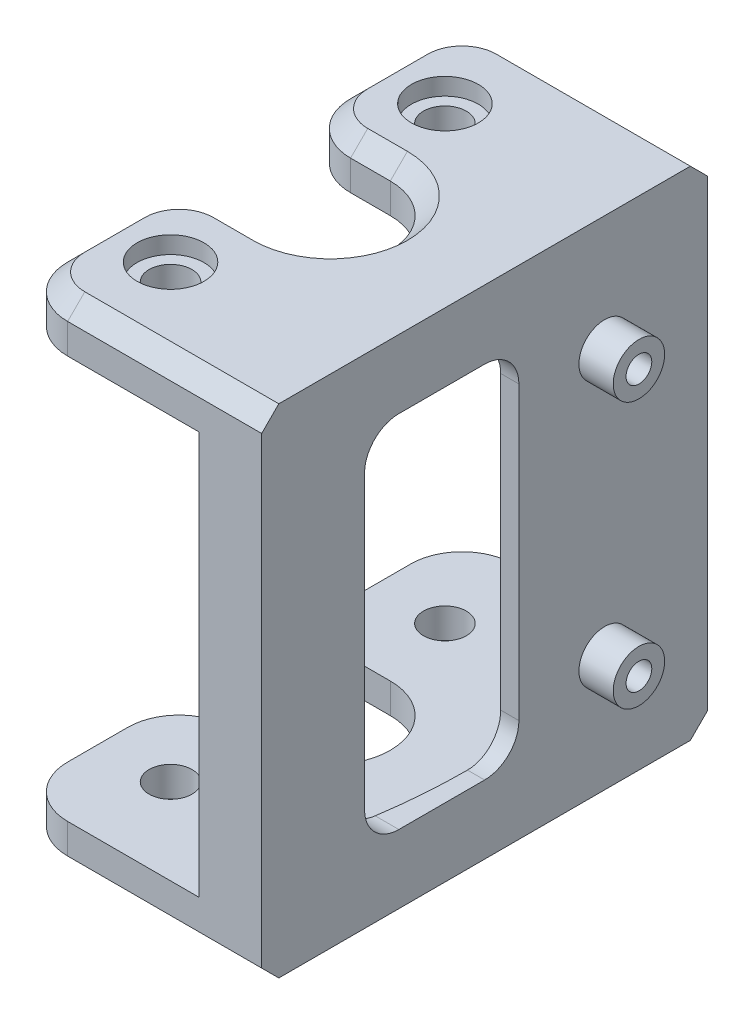
SolidWorks part; units mm, degrees
ref_plane "Спереди" through (0, 0, 0) normal (0, 0, 1) x (1, 0, 0)
ref_plane "Сверху" through (0, 0, 0) normal (0, 1, 0) x (1, 0, 0)
ref_plane "Справа" through (0, 0, 0) normal (1, 0, 0) x (0, 0, -1)
sketch "Эскиз1" plane through (0, 0, 0) normal (0, 1, 0) x (1, 0, 0)
  line L0 (23.6854, 8) -> (23.6854, -8) construction
  line L1 (19.6854, 13) -> (34, 13)
  line L2 (19.6854, 13) -> (19.6854, -13)
  line L3 (19.6854, -13) -> (34, -13)
  line L4 (34, 13) -> (34, -13)
  line L5 (19.6854, 13) -> (34, -13) construction
  line L6 (19.6854, -13) -> (34, 13) construction
  line L7 (25, 3.5) -> (19.6854, 3.5)
  line L8 (25, -3.5) -> (19.6854, -3.5)
  circle A0 centre (0, 0) radius 25 construction
  circle A1 centre (23.6854, 8) radius 1.25
  circle A2 centre (23.6854, -8) radius 1.25
  circle A3 centre (25, 0) radius 3.5
  point P3 (26.8427, 0)
  dimension "D1" = 50
  dimension "D2" = 2.5
  dimension "D3" = 2.5
  dimension "D8" = 7
  dimension "D4" = 16
  dimension "D5" = 4
  dimension "D6" = 34
  dimension "D7" = 26
extrude "Бобышка-Вытянуть1" add sketch "Эскиз1" along normal mid plane 29 contours A3 L8 L2 L3 L4 L1 L7 A2 A1 region at (26.8427, 0, -12.7032)
sketch "Эскиз2" plane through (0, 0, 0) normal (0, 1, 0) x (1, 0, 0)
  circle A0 centre (0, 0) radius 33
  dimension "D1" = 66
extrude "Вырез-Вытянуть1" cut sketch "Эскиз2" against normal mid plane 23.5 contours A0
sketch "Эскиз3" plane through (34, 0, 0) normal (1, 0, 0) x (0, 0, -1)
  line L0 (-13, 0) -> (13, 0) construction
  line L5 (-7, 10.5) -> (2, 10.5)
  line L6 (-7, 10.5) -> (-7, -10.5)
  line L7 (-7, -10.5) -> (2, -10.5)
  line L8 (2, 10.5) -> (2, -10.5)
  line L9 (-7, 10.5) -> (2, -10.5) construction
  line L10 (-7, -10.5) -> (2, 10.5) construction
  line L11 (-13, 14.5) -> (-13, -14.5) construction
  line L12 (13, 14.5) -> (13, -14.5) construction
  circle A0 centre (7, 7.75) radius 0.75
  circle A1 centre (7, -7.75) radius 0.75
  point P0 (-2.5, 0)
  dimension "D5" = 1.5
  dimension "D1" = 6
  dimension "D2" = 5
  dimension "D3" = 21
  dimension "D4" = 6
  dimension "D6" = 15.5
extrude "Вырез-Вытянуть2" cut sketch "Эскиз3" against normal through all
sketch "Эскиз4" plane through (34, 0, 0) normal (1, 0, 0) x (0, 0, -1)
  circle A0 centre (7, 7.75) radius 1.5
  circle A1 centre (7, -7.75) radius 1.5
  circle A11 centre (7, 7.75) radius 0.75
  circle A12 centre (7, 7.75) radius 0.75
  circle A14 centre (7, -7.75) radius 0.75
  circle A15 centre (7, -7.75) radius 0.75
  dimension "D1" = 3
  dimension "D2" = 3
extrude "Бобышка-Вытянуть2" add sketch "Эскиз4" along normal blind 2
fillet "Скругление1" radius 2 4 edges at (33.4697, -10.5, -2) (33.4697, 10.5, -2) (33.1245, 10.5, 7) (33.1245, -10.5, 7)
fillet "Скругление2" radius 3 8 edges at (19.6854, -13.125, -13) (19.6854, -13.125, -3.5) (19.6854, -13.125, 3.5) (19.6854, -13.125, 13) (19.6854, 13.125, -13) (19.6854, 13.125, -3.5) (19.6854, 13.125, 3.5) (19.6854, 13.125, 13)
chamfer "Фаска1" distance 1 angle 45 22 edges at (28.3427, -14.5, -13) (20.5641, -14.5, -12.1213) (19.6854, -14.5, -8.25) (20.5641, -14.5, -4.3787) (23.8427, -14.5, -3.5) (28.5, -14.5, 0) (23.8427, -14.5, 3.5) (20.5641, -14.5, 4.3787) (19.6854, -14.5, 8.25) (20.5641, -14.5, 12.1213) (28.3427, -14.5, 13) (28.3427, 14.5, -13) (20.5641, 14.5, -12.1213) (19.6854, 14.5, -8.25) (20.5641, 14.5, -4.3787) (23.8427, 14.5, -3.5) (28.5, 14.5, 0) (23.8427, 14.5, 3.5) (20.5641, 14.5, 4.3787) (19.6854, 14.5, 8.25) (20.5641, 14.5, 12.1213) (28.3427, 14.5, 13)
sketch "Эскиз5" plane through (0, 14.5, 0) normal (0, 1, 0) x (1, 0, 0)
  circle A0 centre (23.6854, -8) radius 1.95
  circle A1 centre (23.6854, 8) radius 1.95
  dimension "D1" = 3.9
  dimension "D2" = 3.9
extrude "Вырез-Вытянуть3" cut sketch "Эскиз5" against normal blind 1
mirror "Зеркальное отражение1" about plane through (0, 0, 0) normal (0, 1, 0) of "Вырез-Вытянуть3"
equation "\"motor_diameter\"= 30"
equation "\"mm_diameter\"= IIF ( \"motor_diameter\" < 34 , 41 , \"motor_diameter\" + 8 )"
equation "\"upper_shafts_diameter\"= 5"
equation "\"upper_shats_length\"= 180"
equation "\"upper_bearing_d1\"= 10"
equation "\"upper_bearing_d2\"= 5"
equation "\"upper_bearing_h\"= 15"
equation "\"lower_shafts_diameter\"= 5"
equation "\"lower_shafts_length\"= 180"
equation "\"lower_bearing_d1\"= 10"
equation "\"lower_bearing_d2\"= 5"
equation "\"lower_bearing_h\"= 15"
equation "\"print_offset\"= 0.5"
equation "\"bh_screws_d\"= 2"
equation "\"bh_screws_h\"= 20"
equation "\"bh_screws_hh_d\"= 3.4"
equation "\"bh_screws_hh_h\"= 2"
equation "\"bh_nut_d\"= 3.8"
equation "\"bh_nut_h\"= 2"
equation "\"motor_screws_d\"= 3"
equation "\"motor_screws_h\"= 16"
equation "\"motor_screws_hh_d\"= 5.5"
equation "\"motor_screws_hh_h\"= 3"
equation "\"plate_hole_distance\"= 25.4"
equation "\"plate_screws_d\"= 6.5"
equation "\"shafts_diameter\"= IIF ( \"mm_diameter\" < 42 , 42 + 8 , \"mm_diameter\" + 8 )"
equation "\"central_hole_diameter\"= 8"
equation "\"bh_thikness\"= 4"
equation "\"ends_screws_d\"= 4"
equation "\"ends_screws_h\"= 16"
equation "\"ends_screws_hh_d\"= 6.7"
equation "\"ends_screws_hh_h\"= 4.1"
equation "\"ends_nut_d\"= 6.8"
equation "\"ends_nut_h\"= 3"
equation "\"system_radius\" = ( \"shafts_diameter\" + 12 + \"bh_thikness\" / 2 ) / 2"
equation "\"encoder_distance\"= \"system_radius\" + 4"
equation "\"tape_position\"= \"encoder_distance\" - 2 + 3.9 + 1.7 / 2"
equation "\"D1@Эскиз1\"=\"shafts_diameter\""
equation "\"D2@Эскиз1\"=\"bh_screws_d\"+\"print_offset\""
equation "\"D3@Эскиз1\"=\"D2@Эскиз1\""
equation "\"D5@Эскиз1\"=\"bh_thikness\""
equation "\"D6@Эскиз1\"=\"encoder_distance\"-2"
equation "\"D8@Эскиз1\"=\"lower_shafts_diameter\"+2"
equation "\"D1@Бобышка-Вытянуть1\"=\"lower_bearing_h\"+\"bh_thikness\"*2+6"
equation "\"D1@Эскиз2\"=\"system_radius\"*2+2"
equation "\"D1@Вырез-Вытянуть1\"=\"lower_bearing_h\"+\"print_offset\"+\"bh_thikness\"*2"
equation "\"D5@Эскиз3\"=\"bh_screws_d\"-\"print_offset\""
equation "\"D2@Эскиз4\"=\"D1@Эскиз4\""
equation "\"D1@Эскиз5\"=\"bh_screws_hh_d\"+\"print_offset\""
equation "\"D2@Эскиз5\"=\"D1@Эскиз5\""
